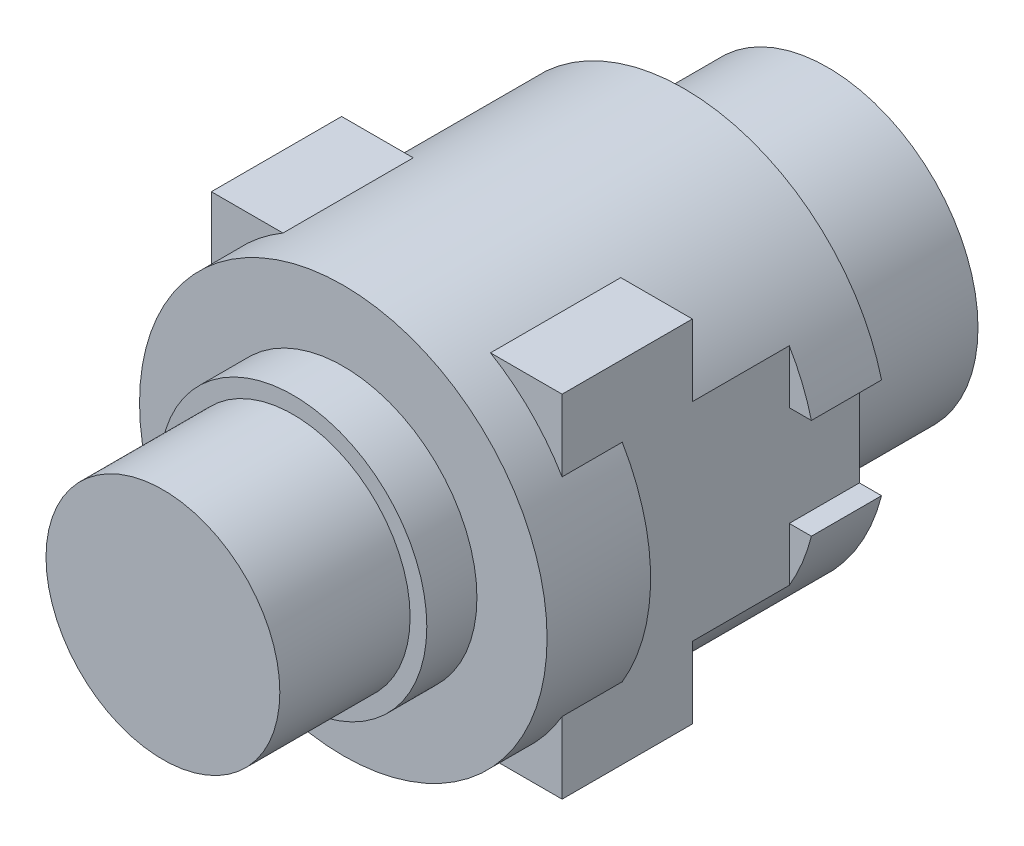
SolidWorks part; units mm, degrees
ref_plane "前视基准面" through (0, 0, 0) normal (0, 0, 1) x (1, 0, 0)
ref_plane "上视基准面" through (0, 0, 0) normal (0, 1, 0) x (1, 0, 0)
ref_plane "右视基准面" through (0, 0, 0) normal (1, 0, 0) x (0, 0, -1)
other "Configuration Table"
sketch "草图1" plane through (0, 0, 0) normal (0, 0, 1) x (1, 0, 0)
  line L13 (-5.25, -5.25) -> (5.25, -5.25)
  line L14 (-5.25, -5.25) -> (-5.25, 5.25)
  line L15 (-5.25, 5.25) -> (5.25, 5.25)
  line L16 (5.25, -5.25) -> (5.25, 5.25)
  line L17 (-5.25, -5.25) -> (5.25, 5.25) construction
  line L18 (-5.25, 5.25) -> (5.25, -5.25) construction
  circle A0 centre (0, 0) radius 6.1
  dimension "D1" = 12.2
  dimension "D2" = 10.5
extrude "凸台-拉伸1" add sketch "草图1" along normal blind 10.2 contours A0
extrude "凸台-拉伸2" add sketch "草图1<5>" against normal blind 3.9 from offset 8.9 contours L15 L16 L13 L14
sketch "草图1<5>" plane through (0, 0, 0) normal (0, 0, 1) x (1, 0, 0) same geometry as "草图1"
extrude "切除-拉伸1" cut sketch "草图1<6>" along normal blind 5 from offset 2.1 contours L16 A0 | L14 A0 region at (-5.5921, 0, 0) region at (5.5921, 0, 0)
sketch "草图1<6>" plane through (0, 0, 0) normal (0, 0, 1) x (1, 0, 0) same geometry as "草图1"
sketch "草图3" plane through (0, 0, 2.1) normal (0, 0, 1) x (1, 0, 0)
  line L0 (5.25, 3.106) -> (5.25, 1.5)
  line L1 (5.25, -3.106) -> (5.25, 3.106) construction
  line L2 (5.25, 1.5) -> (5.25, -1.5)
  line L3 (5.25, -1.5) -> (5.25, -3.106)
  line L4 (5.25, 1.5) -> (5.9127, 1.5)
  line L5 (5.25, -1.5) -> (5.9127, -1.5)
  line L6 (-5.25, 3.106) -> (-5.25, 1.5)
  line L7 (-5.25, -3.106) -> (-5.25, 3.106) construction
  line L8 (-5.25, 1.5) -> (-5.25, -1.5)
  line L9 (-5.25, -1.5) -> (-5.25, -3.106)
  line L10 (-5.25, 1.5) -> (-5.9127, 1.5)
  line L11 (-5.25, -1.5) -> (-5.9127, -1.5)
  line L12 (-5.9127, 1.5) -> (-10.9127, 1.5)
  line L13 (-10.9127, 1.5) -> (-10.9127, -1.5)
  line L14 (-10.9127, -1.5) -> (-5.9127, -1.5)
  arc A0 (5.25, -3.106) -> (5.25, 3.106) centre (0, 0) ccw construction
  arc A1 (-5.25, 3.106) -> (-5.25, -3.106) centre (0, 0) ccw construction
  line M8 (5.25, 3.106) -> (5.25, -3.106)
  arc M9 (5.25, -3.106) -> (5.25, 3.106) centre (0, 0) ccw
  dimension "D1" = 3
  dimension "D2" = 5
extrude "切除-拉伸2" cut sketch "草图3" against normal through all contours L13 L14 L11 L8 L10 L12 | L5 L4 M8 M9 region at (5.6459, 0, 2.1) region at (-8.0813, 0, 2.1)
sketch "草图4" plane through (0, 0, 0) normal (0, 0, -1) x (-1, 0, 0)
  circle A0 centre (0, 0) radius 4.5
  dimension "D1" = 9
extrude "凸台-拉伸3" add sketch "草图4" along normal blind 4.3
sketch "草图5" plane through (0, 0, -4.3) normal (0, 0, -1) x (-1, 0, 0)
  circle A0 centre (0, 0) radius 3
  dimension "D1" = 6
extrude "切除-拉伸3" cut sketch "草图5" against normal blind 2.1
sketch "草图6" plane through (0, 0, 10.2) normal (0, 0, 1) x (1, 0, 0)
  circle A0 centre (0, 0) radius 3.5
  circle A1 centre (0, 0) radius 4
  dimension "D1" = 8
  dimension "D2" = 7
extrude "凸台-拉伸4" add sketch "草图6" along normal blind 1.5
extrude "凸台-拉伸5" add sketch "草图6<2>" along normal blind 5.4 contours A0
sketch "草图6<2>" plane through (0, 0, 10.2) normal (0, 0, 1) x (1, 0, 0) same geometry as "草图6"
